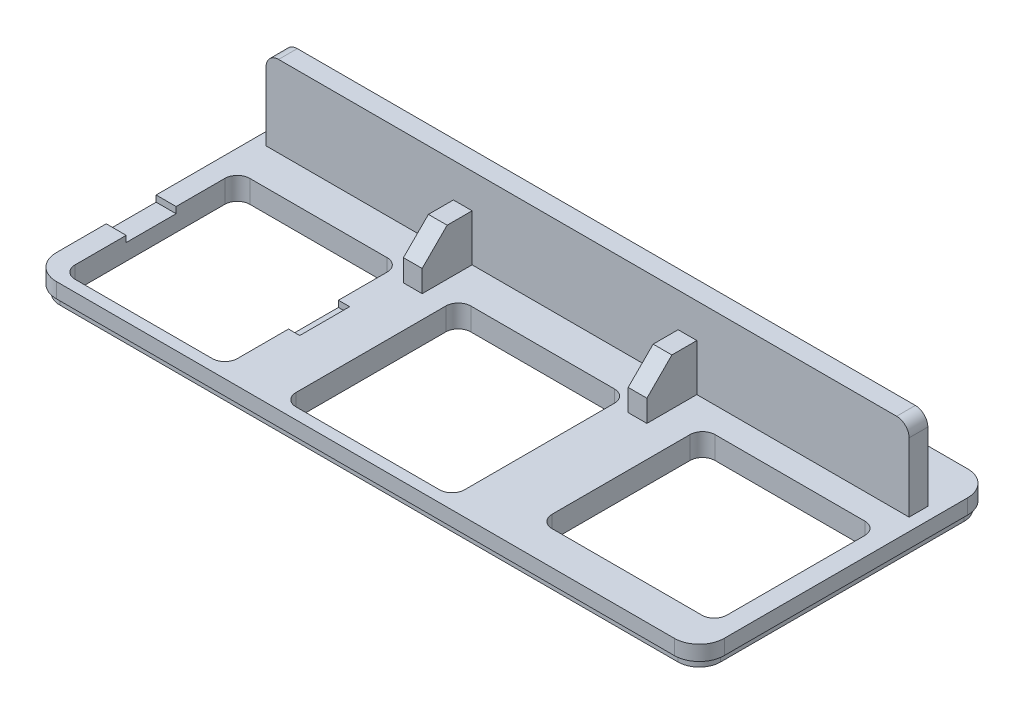
SolidWorks part; units mm, degrees
ref_plane "前视基准面" through (0, 0, 0) normal (0, 0, 1) x (1, 0, 0)
ref_plane "上视基准面" through (0, 0, 0) normal (0, 1, 0) x (1, 0, 0)
ref_plane "右视基准面" through (0, 0, 0) normal (1, 0, 0) x (0, 0, -1)
sketch "草图1" plane through (0, 0, 0) normal (0, 1, 0) x (1, 0, 0)
  line L1 (-26.75, 11.75) -> (26.75, 11.75)
  line L2 (-26.75, 11.75) -> (-26.75, -11.75)
  line L3 (-26.75, -11.75) -> (26.75, -11.75)
  line L4 (26.75, 11.75) -> (26.75, -11.75)
  line L5 (-26.75, 11.75) -> (26.75, -11.75) construction
  line L6 (-26.75, -11.75) -> (26.75, 11.75) construction
  point P0 (0, 0)
  dimension "D1" = 23.5
  dimension "D2" = 53.5
extrude "凸台-拉伸1" add sketch "草图1" along normal blind 1.2
fillet "圆角1" radius 2 4 edges at (-26.75, 0.6, 11.75) (26.75, 0.6, 11.75) (-26.75, 0.6, -11.75) (26.75, 0.6, -11.75)
sketch "草图2" plane through (0, 0, 0) normal (0, -1, 0) x (1, 0, 0)
  line L8 (24.75, 11.45) -> (-24.75, 11.45)
  line L9 (-26.45, 9.75) -> (-26.45, -9.75)
  line L10 (-24.75, -11.45) -> (24.75, -11.45)
  line L11 (26.45, -9.75) -> (26.45, 9.75)
  line L12 (24.75, 11.45) -> (-24.75, 11.45)
  line L13 (-26.45, 9.75) -> (-26.45, -9.75)
  line L14 (-24.75, -11.45) -> (24.75, -11.45)
  line L15 (26.45, -9.75) -> (26.45, 9.75)
  arc A8 (-24.75, 11.45) -> (-26.45, 9.75) centre (-24.75, 9.75) ccw
  arc A9 (-26.45, -9.75) -> (-24.75, -11.45) centre (-24.75, -9.75) ccw
  arc A10 (24.75, -11.45) -> (26.45, -9.75) centre (24.75, -9.75) ccw
  arc A11 (26.45, 9.75) -> (24.75, 11.45) centre (24.75, 9.75) ccw
  arc A12 (-24.75, 11.45) -> (-26.45, 9.75) centre (-24.75, 9.75) ccw
  arc A13 (-26.45, -9.75) -> (-24.75, -11.45) centre (-24.75, -9.75) ccw
  arc A14 (24.75, -11.45) -> (26.45, -9.75) centre (24.75, -9.75) ccw
  arc A15 (26.45, 9.75) -> (24.75, 11.45) centre (24.75, 9.75) ccw
  dimension "D1" = 0.3
extrude "凸台-拉伸2" add sketch "草图2" along normal blind 0.6
sketch "草图3" plane through (0, -0.6, 0) normal (0, -1, 0) x (1, 0, 0)
  line L0 (-26.45, 9.75) -> (-26.45, -9.75) construction
  line L1 (-25.15, 10.85) -> (-12.15, 10.85)
  line L2 (-25.15, 10.85) -> (-25.15, -3.15)
  line L3 (-25.15, -3.15) -> (-12.15, -3.15)
  line L4 (-12.15, 10.85) -> (-12.15, -3.15)
  line L5 (-7.45, 10.85) -> (6.05, 10.85)
  line L6 (-7.45, 10.85) -> (-7.45, -3.15)
  line L7 (-7.45, -3.15) -> (6.05, -3.15)
  line L8 (6.05, 10.85) -> (6.05, -3.15)
  line L9 (11.25, 9.0414) -> (25.25, 9.0414)
  line L10 (11.25, 9.0414) -> (11.25, -4.0086)
  line L11 (11.25, -4.0086) -> (25.25, -4.0086)
  line L12 (25.25, 9.0414) -> (25.25, -4.0086)
  line L13 (26.45, -9.75) -> (26.45, 9.75) construction
  line L14 (24.75, 11.45) -> (-24.75, 11.45) construction
  dimension "D1" = 13
  dimension "D2" = 13.5
  dimension "D3" = 14
  dimension "D4" = 1.3
  dimension "D5" = 19
  dimension "D6" = 1.2
  dimension "D7" = 13.05
  dimension "D8" = 2.4086
  dimension "D9" = 0.6
  dimension "D10" = 14
extrude "切除-拉伸1" cut sketch "草图3" against normal blind 3
fillet "圆角2" radius 1 12 edges at (-25.15, 0.3, 10.85) (-12.15, 0.3, 10.85) (-7.45, 0.3, 10.85) (6.05, 0.3, 10.85) (25.25, 0.3, 9.0414) (11.25, 0.3, 9.0414) (25.25, 0.3, -4.0086) (11.25, 0.3, -4.0086) (6.05, 0.3, -3.15) (-7.45, 0.3, -3.15) (-12.15, 0.3, -3.15) (-25.15, 0.3, -3.15)
sketch "草图4" plane through (0, 1.2, 0) normal (0, 1, 0) x (1, 0, 0)
  line L0 (-26.75, 9.75) -> (-26.75, -9.75) construction
  line L1 (-11.25, -5.75) -> (-26.75, -5.75)
  line L2 (-11.25, -5.75) -> (-11.25, -1.7526)
  line L3 (-11.25, -1.7526) -> (-26.75, -1.7526)
  line L4 (-26.75, -5.75) -> (-26.75, -1.7526)
  line L5 (-24.75, -11.75) -> (24.75, -11.75) construction
  dimension "D1" = 6
  dimension "D2" = 3.9974
  dimension "D3" = 15.5
extrude "切除-拉伸2" cut sketch "草图4" against normal blind 0.5
sketch "草图5" plane through (0, 1.2, 0) normal (0, 1, 0) x (1, 0, 0)
  line L1 (25.75, 6.0546) -> (-25.75, 6.0546)
  line L2 (25.75, 6.0546) -> (25.75, 7.5546)
  line L3 (25.75, 7.5546) -> (-25.75, 7.5546)
  line L4 (-25.75, 6.0546) -> (-25.75, 7.5546)
  line L6 (-26.75, 9.75) -> (-26.75, -1.7526) construction
  line L7 (26.75, -9.75) -> (26.75, 9.75) construction
  line L8 (24.75, 11.75) -> (-24.75, 11.75) construction
  point P4 (0, 0)
  point P5 (25.8873, 6.0435)
  point P6 (-25.8517, 6.0546)
  point P8 (0, 0)
  dimension "D1" = 1.5
  dimension "D2" = 1
  dimension "D3" = 1
  dimension "D4" = 4.1954
extrude "凸台-拉伸3" add sketch "草图5" along normal blind 6.5
fillet "圆角3" radius 1 2 edges at (-25.75, 7.7, -6.8046) (25.75, 7.7, -6.8046)
sketch "草图6" plane through (0, 1.2, 0) normal (0, 1, 0) x (1, 0, 0)
  line L0 (-25.75, 6.0546) -> (25.75, 6.0546) construction
  line L1 (8.75, 6.0546) -> (7.25, 6.0546)
  line L2 (8.75, 6.0546) -> (8.75, 2.0546)
  line L3 (8.75, 2.0546) -> (7.25, 2.0546)
  line L4 (7.25, 6.0546) -> (7.25, 2.0546)
  line L5 (26.75, -9.75) -> (26.75, 9.75) construction
  line L6 (-9.25, 6.0546) -> (-10.75, 6.0546)
  line L7 (-9.25, 6.0546) -> (-9.25, 2.0546)
  line L8 (-9.25, 2.0546) -> (-10.75, 2.0546)
  line L9 (-10.75, 6.0546) -> (-10.75, 2.0546)
  line L10 (-26.75, -5.75) -> (-26.75, -9.75) construction
  dimension "D1" = 4
  dimension "D2" = 1.5
  dimension "D3" = 18
  dimension "D4" = 16
extrude "凸台-拉伸4" add sketch "草图6" along normal blind 3.75
chamfer "倒角1" distance 2 angle 45 2 edges at (-10, 4.95, -2.0546) (8, 4.95, -2.0546)
